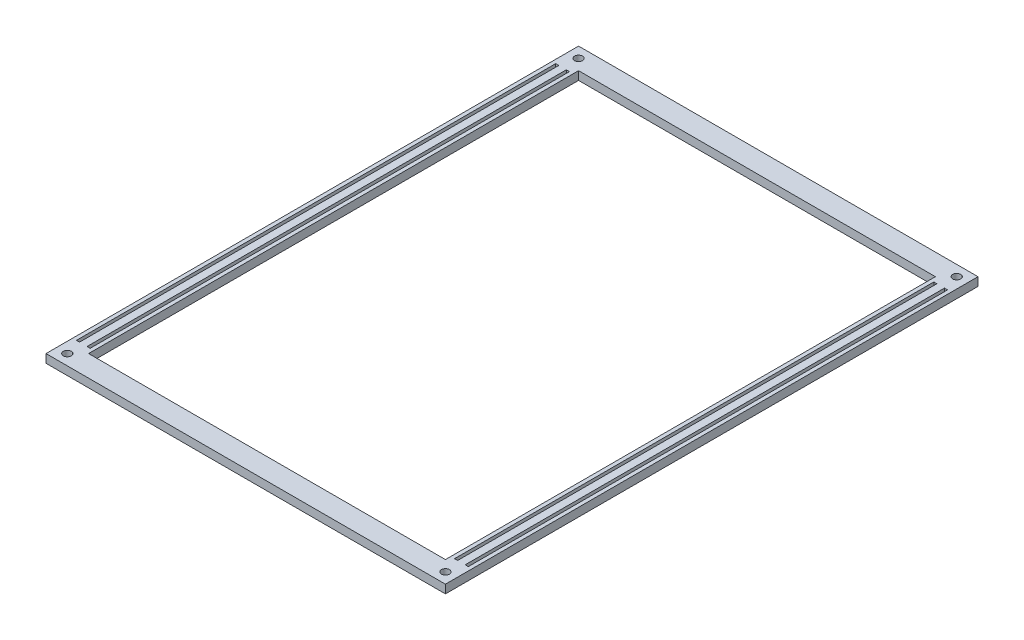
SolidWorks part; units mm, degrees
ref_plane "Front Plane" through (0, 0, 0) normal (0, 0, 1) x (1, 0, 0)
ref_plane "Top Plane" through (0, 0, 0) normal (0, 1, 0) x (1, 0, 0)
ref_plane "Right Plane" through (0, 0, 0) normal (1, 0, 0) x (0, 0, -1)
sketch "Sketch1" plane through (0, 0, 0) normal (0, 1, 0) x (1, 0, 0)
  line L0 (-67, 92) -> (67, 92)
  line L5 (-75, -100) -> (75, -100)
  line L6 (-75, -100) -> (-75, 100)
  line L7 (-75, 100) -> (75, 100)
  line L8 (75, -100) -> (75, 100)
  line L9 (-75, -100) -> (75, 100) construction
  line L10 (-75, 100) -> (75, -100) construction
  line L11 (67, -92) -> (67, 92)
  line L12 (-67, -92) -> (67, -92)
  line L13 (-67, -92) -> (-67, 92)
  line L32 (0, 100) -> (0, -100) construction
  point P0 (0, 0)
  point P5 (0, 0)
  point P12 (0, 0)
  point P31 (0, 0)
  point P35 (0, 0)
  dimension "D2" = 150
  dimension "D3" = 200
  dimension "D1" = 8
extrude "MainBody" add sketch "Sketch1" along normal mid plane 3.175
sketch "Sketch2" plane through (0, 1.5875, 0) normal (0, 1, 0) x (1, 0, 0)
  line L0 (-67, 0) -> (-75, 0) construction
  line L2 (-67, 92) -> (-67, -92) construction
  line L3 (-75, 100) -> (-75, -100) construction
  line L4 (-67, 0) -> (-71, 0) construction
  line L5 (67, 92) -> (-67, 92) construction
  line L6 (-69.5874, -90) -> (-68.4126, -90)
  line L7 (-69.5874, -90) -> (-69.5874, 90)
  line L8 (-69.5874, 90) -> (-68.4126, 90)
  line L9 (-68.4126, -90) -> (-68.4126, 90)
  line L10 (-69.5874, -90) -> (-68.4126, 90) construction
  line L11 (-69.5874, 90) -> (-68.4126, -90) construction
  line L12 (-71, 0) -> (-71, 100) construction
  line L13 (75, 100) -> (-75, 100) construction
  line L14 (-72.4126, -90) -> (-73.5874, -90)
  line L15 (-73.5874, -90) -> (-73.5874, 90)
  line L16 (-72.4126, -90) -> (-72.4126, 90)
  line L17 (-72.4126, 90) -> (-73.5874, 90)
  line L18 (0, 0) -> (0, 100) construction
  line L19 (69.5874, -90) -> (68.4126, -90)
  line L20 (72.4126, -90) -> (73.5874, -90)
  line L21 (68.4126, -90) -> (68.4126, 90)
  line L22 (69.5874, 90) -> (68.4126, 90)
  line L23 (69.5874, -90) -> (69.5874, 90)
  line L24 (73.5874, -90) -> (73.5874, 90)
  line L25 (72.4126, -90) -> (72.4126, 90)
  line L26 (72.4126, 90) -> (73.5874, 90)
  point P7 (-69, 0)
  dimension "D1" = 2
  dimension "D2" = 1.1747
extrude "SheetLock" cut sketch "Sketch2" against normal up to next
sketch "Sketch3" plane through (0, 1.5875, 0) normal (0, 1, 0) x (1, 0, 0)
  line L0 (0, 100) -> (0, -100) construction
  line L1 (75, 100) -> (-75, 100) construction
  line L2 (-75, -100) -> (75, -100) construction
  line L3 (-75, 0) -> (75, 0) construction
  line L4 (-75, 100) -> (-75, -100) construction
  line L5 (75, -100) -> (75, 100) construction
  line L6 (-67, 92) -> (-67, 100) construction
  line L7 (-67, 92) -> (-75, 92) construction
  circle A0 centre (-71, 96) radius 1.5
  circle A1 centre (71, 96) radius 1.5
  circle A2 centre (71, -96) radius 1.5
  circle A3 centre (-71, -96) radius 1.5
  point P17 (0, 0)
  point P19 (-67, 96)
  point P20 (-71, 92)
  dimension "D1" = 3
extrude "SupportHoles" cut sketch "Sketch3" against normal up to next
equation "\"SheetLockLengthOffset\"=2"
equation "\"SheetThickness\"=0.79375"
equation "\"SheetThicknessTolerance\"= 0.015in"
equation "\"D1@Sketch2\"=\"SheetLockLengthOffset\""
equation "\"D2@Sketch2\"=\"SheetThickness\" + \"SheetThicknessTolerance\""
equation "\"LowerBasketWidth\"=150"
equation "\"D2@Sketch1\"=\"LowerBasketWidth\""
equation "\"LowerBasketLength\"=200"
equation "\"D3@Sketch1\"=\"LowerBasketLength\""
equation "\"SupportHoleDiameter\"=3"
equation "\"D1@Sketch3\"=\"SupportHoleDiameter\""
